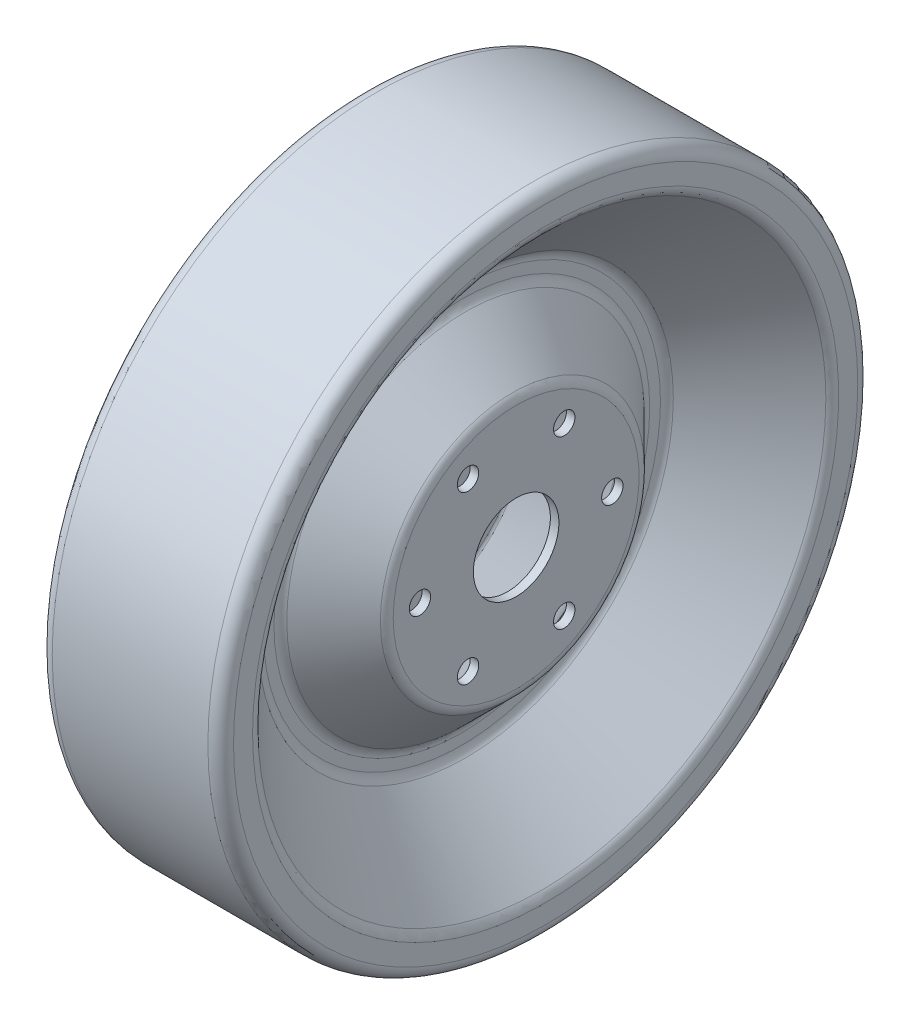
SolidWorks part; units mm, degrees
ref_plane "前视基准面" through (0, 0, 0) normal (0, 0, 1) x (1, 0, 0)
ref_plane "上视基准面" through (0, 0, 0) normal (0, 1, 0) x (1, 0, 0)
ref_plane "右视基准面" through (0, 0, 0) normal (1, 0, 0) x (0, 0, -1)
sketch "草图2" plane through (0, 0, 0) normal (0, 0, 1) x (1, 0, 0)
  line L0 (-73.1447, 0) -> (103.3314, 0) construction
  line L1 (0, 93.7529) -> (0, -60.6637) construction
  line L2 (-14.3, 0) -> (-14.3, 30)
  line L3 (-14.3, 30) -> (-1.6, 42.7)
  line L4 (-1.6, 42.7) -> (-1.6, 47.7)
  line L5 (-1.6, 47.7) -> (-21.2, 67.3)
  line L6 (-21.2, 67.3) -> (-21.2, 76)
  line L7 (-21.2, 76) -> (21.2, 76)
  line L8 (21.2, 67.3) -> (21.2, 76)
  line L9 (1.6, 47.7) -> (21.2, 67.3)
  line L10 (1.6, 42.7) -> (1.6, 47.7)
  line L11 (14.3, 30) -> (1.6, 42.7)
  line L12 (14.3, 0) -> (14.3, 30)
  line L13 (-14.3, 0) -> (14.3, 0)
  point P13 (0, 76)
  dimension "D1" = 152
  dimension "D2" = 28.6
  dimension "D3" = 3.2
  dimension "D4" = 42.4
  dimension "D5" = 5
  dimension "D6" = 135
  dimension "D7" = 30
revolve "旋转1" add sketch "草图2" angle 360 about L0
fillet "圆角1" radius 3 10 edges at (-14.3, 0, 30) (-1.6, 0, 42.7) (-1.6, 0, 47.7) (-21.2, 0, 67.3) (14.3, 0, 30) (1.6, 0, 42.7) (1.6, 0, 47.7) (21.2, 0, 67.3) (21.2, 0, 76) (-21.2, 0, 76)
sketch "草图4" plane through (0, 0, 0) normal (1, 0, 0) x (0, 0, -1)
  circle A0 centre (0, 0) radius 10
  circle A1 centre (0, 0) radius 22.5 construction
  circle A2 centre (22.5, 0) radius 2.5
  circle A3 centre (11.25, -19.4856) radius 2.5
  circle A4 centre (-11.25, -19.4856) radius 2.5
  circle A5 centre (-22.5, 0) radius 2.5
  circle A6 centre (-11.25, 19.4856) radius 2.5
  circle A7 centre (11.25, 19.4856) radius 2.5
  point P18 (0, 0)
  dimension "D1" = 20
  dimension "D2" = 45
  dimension "D3" = 5
  dimension "D4" = 6
extrude "切除-拉伸1" cut sketch "草图4" against normal through all both and the other way through all
shell "抽壳1" thickness 2 removed face at (-14.3, 0, -10) removed face at (-14.3, -19.4856, -13.75) removed face at (-14.3, 0, -25) removed face at (-14.3, 19.4856, -13.75) removed face at (-14.3, 19.4856, 8.75) removed face at (-14.3, 0, 20) removed face at (-14.3, -19.4856, 8.75)
